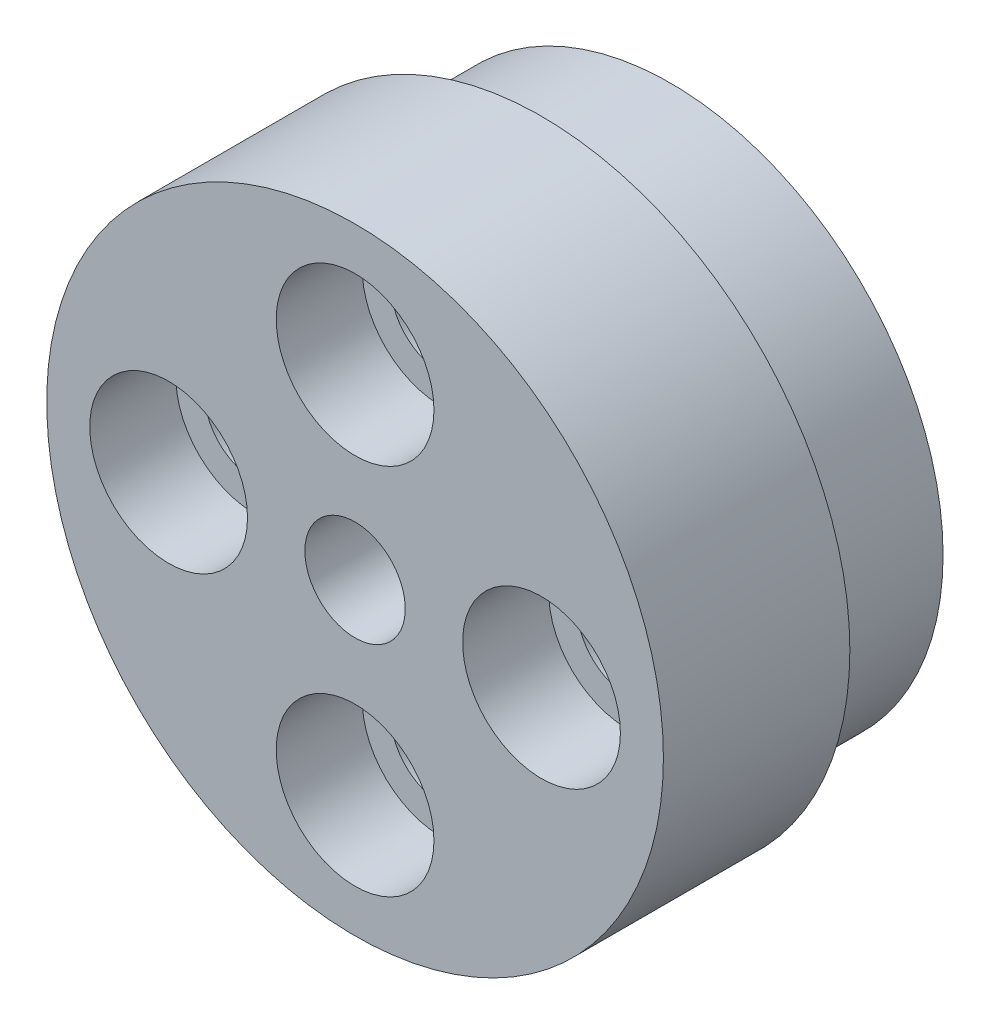
SolidWorks part; units mm, degrees
ref_plane "Front Plane" through (0, 0, 0) normal (0, 0, 1) x (1, 0, 0)
ref_plane "Top Plane" through (0, 0, 0) normal (0, 1, 0) x (1, 0, 0)
ref_plane "Right Plane" through (0, 0, 0) normal (1, 0, 0) x (0, 0, -1)
sketch "Sketch1" plane through (0, 0, 0) normal (0, 0, 1) x (1, 0, 0)
  circle A0 centre (0, 0) radius 10.75
  circle A1 centre (0, 0) radius 9.5
  dimension "D1" = 19
  dimension "25" = 21.5
extrude "Boss-Extrude1" add sketch "Sketch1" against normal blind 11 contours A1 region at (0, 0, 0)
extrude "Boss-Extrude2" add sketch "Sketch1<3>" against normal blind 6.5 contours A0 A1 region at (-10.4459, 0, 0)
sketch "Sketch1<3>" plane through (0, 0, 0) normal (0, 0, 1) x (1, 0, 0) same geometry as "Sketch1"
sketch "Sketch3" plane through (0, 0, -11) normal (0, 0, -1) x (-1, 0, 0)
  circle A0 centre (-6.5, 0) radius 1.75
  circle A1 centre (0, 6.5) radius 1.75
  circle A2 centre (6.5, 0) radius 1.75
  circle A3 centre (0, -6.5) radius 1.75
  circle A4 centre (-6.5, 0) radius 2.75
  circle A5 centre (0, 6.5) radius 2.75
  circle A6 centre (6.5, 0) radius 2.75
  circle A7 centre (0, -6.5) radius 2.75
  dimension "D1" = 3.5
  dimension "D3" = 4
  dimension "D4" = 5.5
  dimension "D2" = 6.5
  dimension "D5" = 4
extrude "Cut-Extrude2" cut sketch "Sketch3" against normal through all contours A1 | A0 | A2 | A3 region at (6.5, 0, -11) region at (0, 6.5, -11) region at (-6.5, 0, -11) region at (0, -6.5, -11)
sketch "Sketch4" plane through (0, 0, -11) normal (0, 0, -1) x (-1, 0, 0)
  circle A0 centre (0, 0) radius 1.75
  dimension "D1" = 3.5
extrude "Cut-Extrude4" cut sketch "Sketch4" against normal through all
extrude "Cut-Extrude5" cut sketch "Sketch3<4>" along normal blind 3 from surface starting at face at (-1.75, 0, 0)
sketch "Sketch3<4>" plane through (0, 0, -11) normal (0, 0, -1) x (-1, 0, 0) same geometry as "Sketch3"
